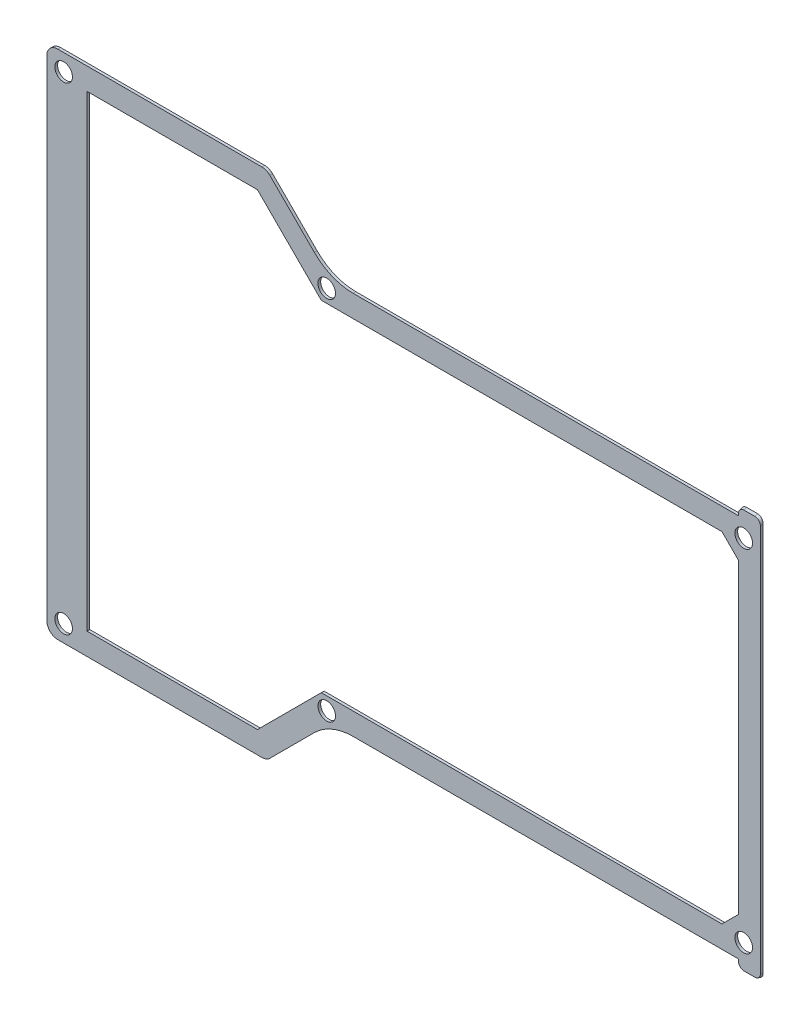
SolidWorks part; units mm, degrees
ref_plane "Front Plane" through (0, 0, 0) normal (0, 0, 1) x (1, 0, 0)
ref_plane "Top Plane" through (0, 0, 0) normal (0, 1, 0) x (1, 0, 0)
ref_plane "Right Plane" through (0, 0, 0) normal (1, 0, 0) x (0, 0, -1)
sketch "Sketch1" plane through (0, 0, 0) normal (0, 0, 1) x (1, 0, 0)
  line L0 (20, -100.2696) -> (0, -100.2696) construction
  line L1 (31.61, -88.6596) -> (20, -100.2696) construction
  line L2 (104.455, -88.6596) -> (31.61, -88.6596) construction
  line L3 (104.455, -88.6596) -> (107.455, -85.6596) construction
  line L4 (107.455, -29.8746) -> (107.455, -85.6596) construction
  line L5 (104.455, -26.8746) -> (107.455, -29.8746) construction
  line L6 (31.605, -26.8746) -> (104.455, -26.8746) construction
  line L7 (20, -15.2696) -> (31.605, -26.8746) construction
  line L8 (0, -100.2696) -> (0, -15.2696) construction
  line L9 (0, -15.2696) -> (20, -15.2696) construction
  line L10 (30.3329, -19.9457) -> (22.2426, -11.8554) construction
  line L11 (107.455, -22.8746) -> (37.404, -22.8746) construction
  line L12 (108.455, -21.3054) -> (110.455, -21.3054) construction
  line L15 (37.409, -92.6596) -> (107.455, -92.6596) construction
  line L16 (22.2426, -103.6838) -> (30.3379, -95.5885) construction
  line L17 (-16.3, -104.2696) -> (20.8284, -104.2696) construction
  line L18 (-18.3, -13.2696) -> (-18.3, -102.2696) construction
  line L19 (20.8284, -11.2696) -> (-16.3, -11.2696) construction
  line L20 (20, -100.2696) -> (0, -100.2696)
  line L21 (31.61, -88.6596) -> (20, -100.2696)
  line L22 (104.455, -88.6596) -> (31.61, -88.6596)
  line L23 (104.455, -88.6596) -> (107.455, -85.6596)
  line L24 (107.455, -29.8746) -> (107.455, -85.6596)
  line L25 (104.455, -26.8746) -> (107.455, -29.8746)
  line L26 (31.605, -26.8746) -> (104.455, -26.8746)
  line L27 (20, -15.2696) -> (31.605, -26.8746)
  line L28 (0, -100.2696) -> (0, -15.2696)
  line L29 (0, -15.2696) -> (20, -15.2696)
  line L30 (30.3329, -19.9457) -> (22.2426, -11.8554)
  line L31 (107.455, -22.8746) -> (37.404, -22.8746)
  line L32 (108.455, -21.3054) -> (110.455, -21.3054)
  line L33 (107.455, -94.2295) -> (111.455, -94.2295)
  line L34 (111.455, -94.2295) -> (111.455, -21.3054)
  line L35 (37.409, -92.6596) -> (107.455, -92.6596)
  line L36 (22.2426, -103.6838) -> (30.3379, -95.5885)
  line L37 (-16.3, -104.2696) -> (20.8284, -104.2696)
  line L38 (-18.3, -13.2696) -> (-18.3, -102.2696)
  line L39 (20.8284, -11.2696) -> (-16.3, -11.2696)
  line L40 (111.455, -21.3054) -> (107.455, -21.3054)
  line L41 (107.455, -94.2295) -> (107.455, -92.6596)
  line L42 (107.455, -21.3054) -> (107.455, -22.8746)
  arc A0 (22.2426, -11.8554) -> (20.8284, -11.2696) centre (20.8284, -13.2696) ccw construction
  arc A1 (30.3329, -19.9457) -> (37.404, -22.8746) centre (37.404, -12.8746) ccw construction
  arc A2 (37.409, -92.6596) -> (30.3379, -95.5885) centre (37.409, -102.6596) ccw construction
  arc A3 (20.8284, -104.2696) -> (22.2426, -103.6838) centre (20.8284, -102.2696) ccw construction
  arc A4 (-18.3, -102.2696) -> (-16.3, -104.2696) centre (-16.3, -102.2696) ccw construction
  arc A5 (-16.3, -11.2696) -> (-18.3, -13.2696) centre (-16.3, -13.2696) ccw construction
  arc A6 (22.2426, -11.8554) -> (20.8284, -11.2696) centre (20.8284, -13.2696) ccw
  arc A7 (30.3329, -19.9457) -> (37.404, -22.8746) centre (37.404, -12.8746) ccw
  arc A8 (37.409, -92.6596) -> (30.3379, -95.5885) centre (37.409, -102.6596) ccw
  arc A9 (20.8284, -104.2696) -> (22.2426, -103.6838) centre (20.8284, -102.2696) ccw
  arc A10 (-18.3, -102.2696) -> (-16.3, -104.2696) centre (-16.3, -102.2696) ccw
  arc A11 (-16.3, -11.2696) -> (-18.3, -13.2696) centre (-16.3, -13.2696) ccw
  circle A12 centre (108.4121, -25.9175) radius 1.25 construction
  circle A13 centre (32.5911, -24.494) radius 1.25 construction
  circle A14 centre (-15.2393, -14.3303) radius 1.25 construction
  circle A15 centre (-15.2393, -101.2089) radius 1.25 construction
  circle A16 centre (32.5961, -91.0402) radius 1.25 construction
  circle A17 centre (108.4121, -89.6167) radius 1.25 construction
  circle A18 centre (108.4121, -25.9175) radius 1.25 construction
  circle A19 centre (32.5911, -24.494) radius 1.25 construction
  circle A20 centre (-15.2393, -14.3303) radius 1.25 construction
  circle A21 centre (-15.2393, -101.2089) radius 1.25 construction
  circle A22 centre (32.5961, -91.0402) radius 1.25 construction
  circle A23 centre (108.4121, -89.6167) radius 1.25 construction
  circle A24 centre (-15.2393, -101.2089) radius 1.6
  circle A25 centre (32.5961, -91.0402) radius 1.6
  circle A26 centre (108.4121, -89.6167) radius 1.6
  circle A27 centre (108.4121, -25.9175) radius 1.6
  circle A28 centre (32.5911, -24.494) radius 1.6
  circle A29 centre (-15.2393, -14.3303) radius 1.6
extrude "Boss-Extrude1" add sketch "Sketch1" along normal blind 0.5 contours L39 A11 L38 A10 L37 A9 L36 A8 L35 L41 L33 L34 L40 L32 L42 L31 A7 L30 A6 A29 A28 A27 A26 A25 A24 L28 L29 L27 L26 L25 L24 L23 L22 L21 L20 region at (33.5161, -22.2609, 0)
sketch "Sketch2" plane through (111.455, 0, 0) normal (1, 0, 0) x (0, 0, -1)
  line L2 (28.78, -11.2696) -> (0, -21.3054)
  line L3 (0, -94.2295) -> (28.78, -104.2696)
  line L4 (0, -21.3054) -> (-2.5092, -22.1804)
  line L5 (-2.5092, -22.1804) -> (-2.2343, -18.9333)
  line L6 (-2.2343, -18.9333) -> (1.8663, -18.9333)
  line L7 (1.8663, -18.9333) -> (0, -21.3054)
  line L8 (0, -94.2295) -> (-3.7144, -92.9337)
  line L9 (-3.7144, -92.9337) -> (-3.7144, -98.6628)
  line L10 (-3.7144, -98.6628) -> (4.2666, -98.6628)
  line L11 (4.2666, -98.6628) -> (0, -94.2295)
extrude "Cut-Extrude3" cut sketch "Sketch2" against normal blind 10 contours L10 L11 L8 L9 | L7 L6 L5 L4 | L4 | L8 region at (111.455, -20.2093, 0.7767) region at (111.455, -96.4678, 0.815)
fillet "Fillet1" radius 1 4 edges at (107.455, -94.1422, 0.25) (111.455, -94.1422, 0.25) (107.455, -21.3926, 0.25) (111.455, -21.3926, 0.25)
sketch "Sketch3" plane through (0, 0, 0.5) normal (0, 0, 1) x (1, 0, 0)
  line L0 (0, -100.2696) -> (0, -15.2696) construction
  line L2 (104.455, -88.6596) -> (31.61, -88.6596) construction
  line L3 (31.61, -88.6596) -> (20, -100.2696) construction
  line L5 (31.605, -26.8746) -> (104.455, -26.8746) construction
  line L6 (20, -15.2696) -> (31.605, -26.8746) construction
  line L7 (0, -100.2696) -> (0, -15.2696)
  line L8 (20, -100.2696) -> (31.61, -87.476)
  line L9 (104.455, -88.6596) -> (31.61, -88.6596)
  line L10 (31.61, -88.6596) -> (20, -100.2696)
  line L11 (31.61, -87.476) -> (104.455, -88.6596)
  line L12 (31.605, -26.8746) -> (104.455, -26.8746)
  line L13 (20, -15.2696) -> (31.605, -26.8746)
  line L14 (0, -15.2696) -> (-11, -15.2696)
  line L15 (-11, -15.2696) -> (-11, -100.2696)
  line L16 (-11, -100.2696) -> (0, -100.2696)
  line M29 (0, -100.2696) -> (0, -15.2696)
extrude "Cut-Extrude4" cut sketch "Sketch3" against normal blind 10 contours L15 L16 L14 M29 region at (-5.5, -57.7696, 0.5)
